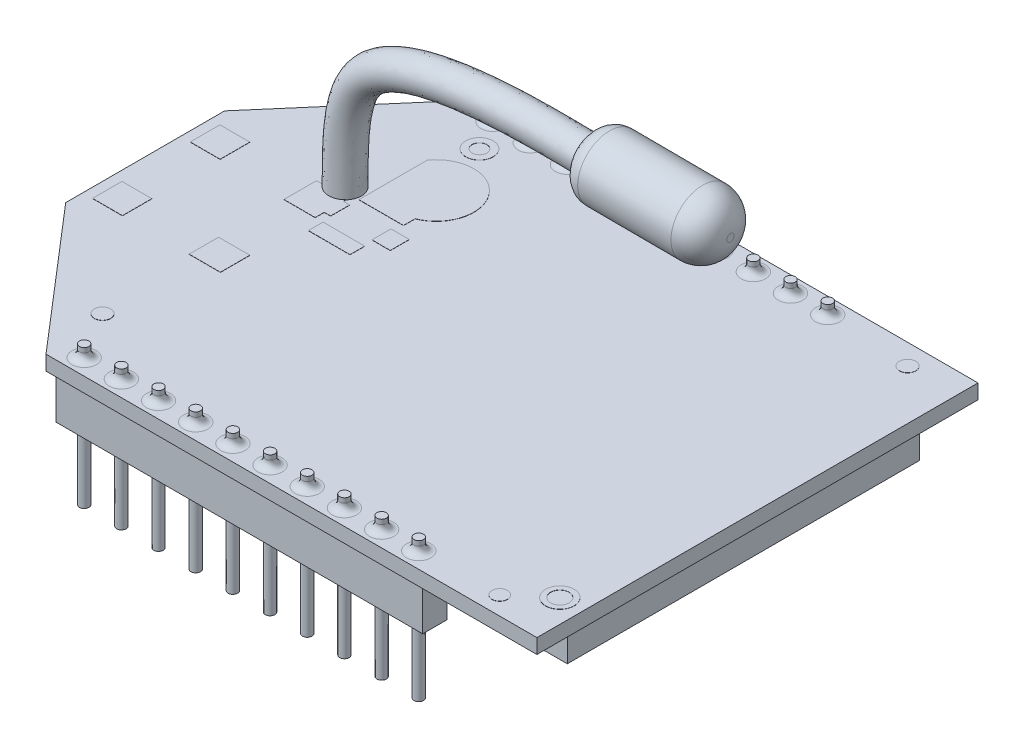
SolidWorks part; units mm, degrees
ref_plane "Front Plane" through (0, 0, 0) normal (0, 0, 1) x (1, 0, 0)
ref_plane "Top Plane" through (0, 0, 0) normal (0, 1, 0) x (1, 0, 0)
ref_plane "Right Plane" through (0, 0, 0) normal (1, 0, 0) x (0, 0, -1)
sketch "Sketch2" plane through (0, 0, 0) normal (0, 1, 0) x (1, 0, 0)
  line L0 (0, 0) -> (-34.8989, 0) construction
  line L1 (20.1484, 0.325) -> (20.1484, -11.865)
  line L2 (20.1484, -11.865) -> (-6.2616, -11.865)
  line L3 (-6.2616, -11.865) -> (-12.7916, -4.275)
  line L4 (-12.7916, -4.275) -> (-12.7916, 4.275)
  line L5 (-6.2616, 11.865) -> (-12.7916, 4.275)
  line L6 (20.1484, 11.865) -> (-6.2616, 11.865)
  line L7 (20.1484, 0.325) -> (20.1484, 11.865)
  line L8 (0, 0) -> (27.7579, 0) construction
  point P9 (-12.7916, 0)
  dimension "D1" = 12.19
  dimension "D2" = 32.94
  dimension "D3" = 7.59
  dimension "D4" = 6.53
extrude "Boss-Extrude1" add sketch "Sketch2" along normal blind 0.79
sketch "Sketch4" plane through (0, 0.79, 0) normal (0, 1, 0) x (1, 0, 0)
  line L0 (0, 0) -> (20.1484, 0) construction
  line L1 (20.1484, -11.865) -> (20.1484, 11.865) construction
  line L2 (20.1484, 11) -> (-6.1506, 11) construction
  line L3 (-12.7916, 4.275) -> (-12.7916, -4.275) construction
  circle A0 centre (-5.0716, 11) radius 0.255
  circle A1 centre (-3.0716, 11) radius 0.255
  circle A2 centre (-1.0716, 11) radius 0.255
  circle A3 centre (0.9284, 11) radius 0.255
  circle A4 centre (2.9284, 11) radius 0.255
  circle A5 centre (4.9284, 11) radius 0.255
  circle A6 centre (6.9284, 11) radius 0.255
  circle A7 centre (8.9284, 11) radius 0.255
  circle A8 centre (10.9284, 11) radius 0.255
  circle A9 centre (12.9284, 11) radius 0.255
  circle A10 centre (12.9284, -11) radius 0.255
  circle A11 centre (10.9284, -11) radius 0.255
  circle A12 centre (8.9284, -11) radius 0.255
  circle A13 centre (6.9284, -11) radius 0.255
  circle A14 centre (4.9284, -11) radius 0.255
  circle A15 centre (2.9284, -11) radius 0.255
  circle A16 centre (0.9284, -11) radius 0.255
  circle A17 centre (-1.0716, -11) radius 0.255
  circle A18 centre (-3.0716, -11) radius 0.255
  circle A19 centre (-5.0716, -11) radius 0.255
  dimension "D2" = 0.51
  dimension "D1" = 11
  dimension "D3" = 7.72
  dimension "D4" = 10
extrude "Boss-Extrude2" add sketch "Sketch4" along normal blind 0.65 and the other way blind 6.85
fillet "Fillet1" radius 0.4 20 edges at (-5.0716, 0.79, 10.745) (-3.0716, 0.79, 10.745) (-1.0716, 0.79, 10.745) (0.9284, 0.79, 10.745) (2.9284, 0.79, 10.745) (4.9284, 0.79, 10.745) (6.9284, 0.79, 10.745) (8.9284, 0.79, 10.745) (10.9284, 0.79, 10.745) (12.9284, 0.79, 10.745) (8.9284, 0.79, -11.255) (10.9284, 0.79, -11.255) (12.9284, 0.79, -11.255) (6.9284, 0.79, -11.255) (4.9284, 0.79, -11.255) (2.9284, 0.79, -11.255) (0.9284, 0.79, -11.255) (-1.0716, 0.79, -11.255) (-3.0716, 0.79, -11.255) (-5.0716, 0.79, -11.255)
sketch "Sketch5" plane through (0, 0, 0) normal (0, -1, 0) x (1, 0, 0)
  line L0 (0, 0) -> (-12.7916, 0) construction
  line L1 (-12.7916, -4.275) -> (-12.7916, 4.275) construction
  line L2 (0, 0) -> (20.1484, 0) construction
  line L3 (20.1484, 11.865) -> (20.1484, -11.865) construction
  line L5 (19.3984, -9.48) -> (-5.9033, -9.48)
  line L6 (19.3984, -9.48) -> (19.3984, 9.48)
  line L7 (19.3984, 9.48) -> (-5.9033, 9.48)
  line L8 (-5.9033, -9.48) -> (-5.9033, 9.48)
  line L9 (19.3984, -9.48) -> (-5.9033, 9.48) construction
  line L10 (19.3984, 9.48) -> (-5.9033, -9.48) construction
  point P5 (6.7475, 0)
  point P13 (3.9284, 11)
  dimension "D1" = 0.75
  dimension "D2" = 18.96
extrude "Boss-Extrude3" add sketch "Sketch5" along normal blind 2
sketch "Sketch7" plane through (0, 0, 0) normal (0, -1, 0) x (1, 0, 0)
  line L0 (0, 0) -> (-12.7916, 0) construction
  line L1 (-12.7916, -4.275) -> (-12.7916, 4.275) construction
  line L2 (-5.0716, 11) -> (12.9284, 11) construction
  line L3 (-5.0716, -11) -> (12.9284, -11) construction
  line L4 (13.791, 10.3474) -> (-5.9343, 10.3474)
  line L5 (13.791, 10.3474) -> (13.791, 11.6526)
  line L6 (13.791, 11.6526) -> (-5.9343, 11.6526)
  line L7 (-5.9343, 10.3474) -> (-5.9343, 11.6526)
  line L8 (13.791, 10.3474) -> (-5.9343, 11.6526) construction
  line L9 (13.791, 11.6526) -> (-5.9343, 10.3474) construction
  line L10 (13.791, -11.6526) -> (-5.9343, -11.6526)
  line L11 (-5.9343, -10.3474) -> (-5.9343, -11.6526)
  line L12 (13.791, -10.3474) -> (-5.9343, -10.3474)
  line L13 (13.791, -10.3474) -> (13.791, -11.6526)
  line L14 (13.791, -11.6526) -> (-5.9343, -10.3474) construction
  line L15 (13.791, -10.3474) -> (-5.9343, -11.6526) construction
  point P9 (3.9284, 11)
  point P20 (3.9284, -11)
extrude "Boss-Extrude4" add sketch "Sketch7" along normal blind 2.32
sketch "Sketch9" plane through (0, 0.79, 0) normal (0, 1, 0) x (1, 0, 0)
  line L0 (-5.0354, 7.4189) -> (-5.0354, 3.7398)
  line L1 (-12.2573, 3.4862) -> (-10.6502, 3.4862)
  line L2 (-12.2573, 3.4862) -> (-12.2573, 1.8913)
  line L3 (-12.2573, 1.8913) -> (-10.6502, 1.8913)
  line L4 (-10.6502, 3.4862) -> (-10.6502, 1.8913)
  line L5 (-7.0585, 3.4862) -> (-5.3784, 3.4862)
  line L6 (-7.0585, 3.4862) -> (-7.0585, 1.733)
  line L7 (-7.0585, 1.733) -> (-5.3784, 1.733)
  line L8 (-5.3784, 3.4862) -> (-5.3784, 3.2427)
  line L9 (-5.0354, 2.22) -> (-5.3784, 2.22)
  line L10 (-5.0354, 2.22) -> (-5.0354, 3.2427)
  line L11 (-5.0354, 3.2427) -> (-5.3784, 3.2427)
  line L13 (-4.9522, 1.733) -> (-2.712, 1.733)
  line L14 (-4.9522, 1.733) -> (-4.9522, 0.9416)
  line L15 (-4.9522, 0.9416) -> (-2.712, 0.9416)
  line L16 (-2.712, 1.733) -> (-2.712, 0.9416)
  line L17 (-2.8094, 3.2427) -> (-1.8232, 3.2427)
  line L18 (-2.8094, 3.2427) -> (-2.8094, 2.22)
  line L19 (-2.8094, 2.22) -> (-1.8232, 2.22)
  line L20 (-1.8232, 3.2427) -> (-1.8232, 2.22)
  line L21 (-7.0585, -1.7833) -> (-5.3784, -1.7833)
  line L22 (-7.0585, -1.7833) -> (-7.0585, -3.3649)
  line L23 (-7.0585, -3.3649) -> (-5.3784, -3.3649)
  line L24 (-5.3784, -1.7833) -> (-5.3784, -3.3649)
  line L25 (-10.6502, -3.3649) -> (-12.2573, -3.3649)
  line L26 (-10.6502, -3.3649) -> (-10.6502, -1.7833)
  line L27 (-10.6502, -1.7833) -> (-12.2573, -1.7833)
  line L28 (-12.2573, -3.3649) -> (-12.2573, -1.7833)
  line L29 (-5.0354, 3.7398) -> (-2.6309, 3.7398)
  line L30 (-2.6309, 3.7398) -> (-2.6309, 4.3658)
  line L31 (-5.3784, 2.22) -> (-5.3784, 1.733)
  arc A0 (-2.6309, 4.3658) -> (-5.0354, 7.4189) centre (-3.3821, 6.2476) ccw
  circle A1 centre (-6.6193, -8.4671) radius 0.4392
  circle A2 centre (17.1667, -10.8838) radius 0.4156
  circle A3 centre (18.909, -9.3904) radius 0.7699
  circle A4 centre (18.909, -9.3904) radius 0.4982
  circle A5 centre (-4.1612, 9.3531) radius 0.7393
  circle A6 centre (-4.1612, 9.3531) radius 0.3965
  circle A7 centre (17.4774, 10.7508) radius 0.4422
extrude "Boss-Extrude7" add sketch "Sketch9" along normal blind 0.01
sketch "Sketch10" plane through (0, 0.79, 0) normal (0, 1, 0) x (1, 0, 0)
  line L0 (-12.7916, 4.275) -> (-12.7916, -4.275) construction
  line L1 (20.1484, 11.865) -> (-6.2616, 11.865) construction
  circle A0 centre (-6.0216, 3.985) radius 0.875
  dimension "D1" = 1.75
  dimension "D2" = 6.77
  dimension "D3" = 7.88
ref_plane "Plane1" through (0, 0, -3.99) normal (0, 0, 1) x (1, 0, 0)
sketch "Sketch13" plane through (0, 0, -3.99) normal (0, 0, 1) x (1, 0, 0)
  line L0 (-6.0116, 0.79) -> (-6.0116, 8.79) construction
  line L1 (-5.1466, 0.79) -> (-6.8966, 0.79) construction
  line L2 (-6.0116, 8.79) -> (7.2084, 8.79) construction
  spline S0 degree 3 poles (-6.0116, 0.79) (-5.9889, 3.3139) (-6.0464, 9.21) (4.7054, 8.8228) (7.2084, 8.79) knots 0 0 0 0 0.234578 0.651136 0.651136 0.651136 0.651136
  dimension "D1" = 6.78
  dimension "D2" = 8
  dimension "D3" = 20
sweep "Sweep2" add profiles "Sketch10" path "Sketch13"
sketch "Sketch14" plane through (7.1722, -0.0294, 0) normal (1, -0.0041, 0) x (0, 0, -1)
  circle A0 centre (3.985, 8.8295) radius 1.7
  dimension "D1" = 3.4
extrude "Boss-Extrude8" add sketch "Sketch14" along normal blind 7.5
fillet "Fillet2" radius 1.5 1 edges at (14.7153, 10.4692, -3.985)
fillet "Fillet3" radius 1 1 edges at (7.2154, 10.5, -3.985)
